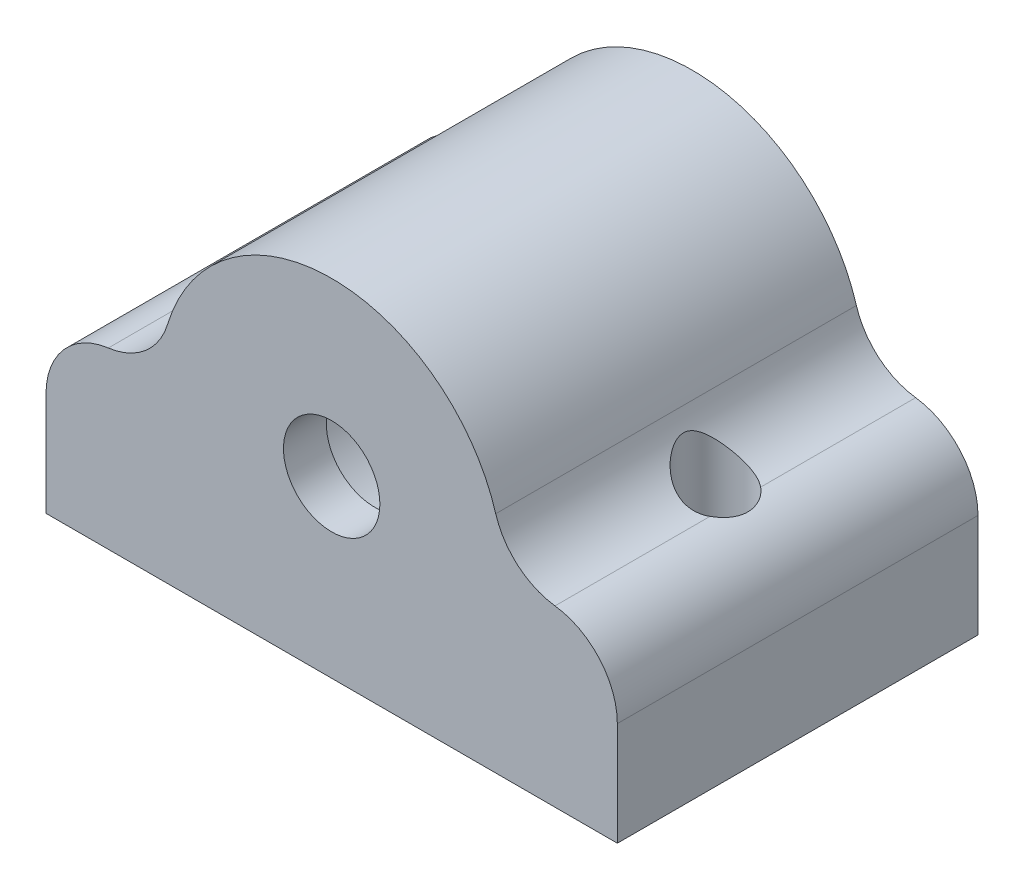
SolidWorks part; units mm, degrees
ref_plane "Front Plane" through (0, 0, 0) normal (0, 0, 1) x (1, 0, 0)
ref_plane "Top Plane" through (0, 0, 0) normal (0, 1, 0) x (1, 0, 0)
ref_plane "Right Plane" through (0, 0, 0) normal (1, 0, 0) x (0, 0, -1)
sketch "Sketch1" plane through (0, 0, 0) normal (0, 0, 1) x (1, 0, 0)
  line L0 (-40, -24.5) -> (40, -24.5)
  line L1 (-40, -24.5) -> (-40, 0)
  line L2 (-40, 0) -> (-24, 0)
  line L3 (40, -24.5) -> (40, 0)
  line L4 (40, 0) -> (24, 0)
  circle A0 centre (0, 0) radius 14
  circle A1 centre (0, 0) radius 24
  point P6 (0, -24.5)
  dimension "D1" = 28
  dimension "D2" = 10
  dimension "D3" = 24.5
  dimension "D4" = 80
extrude "Boss-Extrude1" add sketch "Sketch1" along normal blind 50.5 contours A1 A0 | A1 L2 L1 L0 L3 L4 region at (-39.1633, -12.25, 0) region at (0, 23.3212, 0)
sketch "Sketch2" plane through (0, 0, 0) normal (0, 1, 0) x (1, 0, 0)
  line L0 (40, -50.5) -> (40, 0) construction
  line L3 (-40, -50.5) -> (-40, 0) construction
  circle A0 centre (28.5, -25.25) radius 4.5
  circle A1 centre (-28.5, -25.25) radius 4.5
  point P5 (40, -25.25)
  point P7 (-40, -25.25)
  dimension "D2" = 9
  dimension "D3" = 9
  dimension "D1" = 11.5
  dimension "D4" = 11.5
sketch "Sketch5" plane through (0, 0, 50.5) normal (0, 0, 1) x (1, 0, 0)
  circle A0 centre (0, 0) radius 14
  circle A1 centre (0, 0) radius 6.75
extrude "Boss-Extrude3" add sketch "Sketch5" against normal blind 6
fillet "Fillet3" radius 4 1 edges at (14, 0, 44.5)
fillet "Fillet1" radius 10 2 edges at (40, 0, 25.25) (-40, 0, 25.25)
fillet "Fillet2" radius 10 2 edges at (-24, 0, 25.25) (24, 0, 25.25)
extrude "Cut-Extrude1" cut sketch "Sketch2" against normal blind 50.5 and the other way blind 50.5
sketch "Sketch4" plane through (0, -24.5, 0) normal (0, -1, 0) x (1, 0, 0)
  line L1 (-40, 50.5) -> (40, 50.5)
  line L2 (-40, 50.5) -> (-40, 0)
  line L3 (-40, 0) -> (40, 0)
  line L4 (40, 50.5) -> (40, 0)
  circle A0 centre (-28.5, 25.25) radius 2.05
  circle A1 centre (28.5, 25.25) radius 2.05
extrude "Boss-Extrude2" add sketch "Sketch4" against normal blind 5
